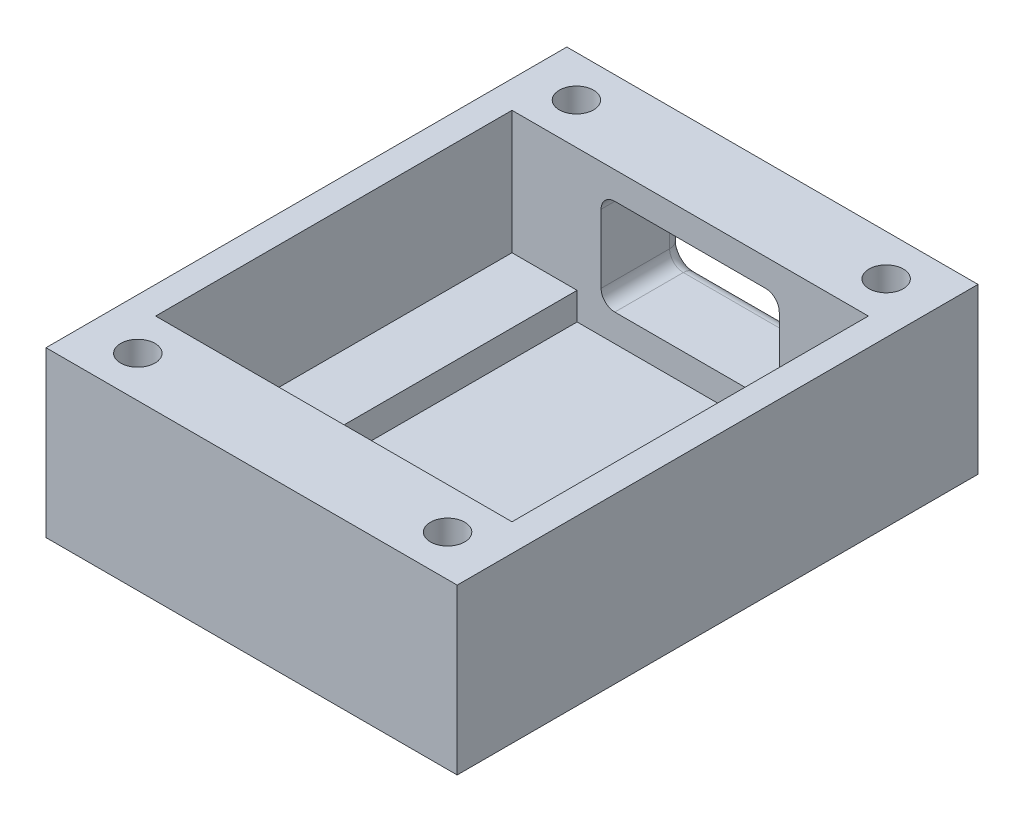
SolidWorks part; units mm, degrees
ref_plane "前视基准面" through (0, 0, 0) normal (0, 0, 1) x (1, 0, 0)
ref_plane "上视基准面" through (0, 0, 0) normal (0, 1, 0) x (1, 0, 0)
ref_plane "右视基准面" through (0, 0, 0) normal (1, 0, 0) x (0, 0, -1)
sketch "草图1" plane through (0, 0, 0) normal (0, 1, 0) x (1, 0, 0)
  line L0 (-50.4212, 0) -> (58.0073, 0) construction
  line L1 (-15, 19) -> (15, 19)
  line L2 (-15, 19) -> (-15, -19)
  line L3 (-15, -19) -> (15, -19)
  line L4 (15, 19) -> (15, -19)
  line L5 (0, 45.3104) -> (0, -50.4975) construction
  line L6 (-8.25, 13) -> (-8.25, -13)
  line L7 (-13, 13) -> (13, 13)
  line L8 (-13, 13) -> (-13, -13)
  line L9 (-13, -13) -> (13, -13)
  line L10 (13, 13) -> (13, -13)
  line L15 (8.25, 13) -> (8.25, -13)
  circle A0 centre (-11.3, 16) radius 1.25
  circle A1 centre (11.3, 16) radius 1.25
  circle A2 centre (11.3, -16) radius 1.25
  circle A3 centre (-11.3, -16) radius 1.25
  circle A4 centre (-11.3, 16) radius 2.25
  circle A5 centre (11.3, 16) radius 2.25
  circle A6 centre (11.3, -16) radius 2.25
  circle A7 centre (-11.3, -16) radius 2.25
  point P18 (-8.25, 13)
  point P19 (8.25, 13)
  point P20 (8.25, -13)
  point P21 (-8.25, -13)
  dimension "D5" = 2.5
  dimension "D6" = 4.5
  dimension "D1" = 26
  dimension "D2" = 16.5
  dimension "D3" = 30
  dimension "D4" = 38
  dimension "D7" = 3
  dimension "D8" = 3.7
extrude "凸台-拉伸1" add sketch "草图1" along normal blind 12 contours L1 L4 L3 L2
ref_plane "基准面1" through (0, 3, 0) normal (0, 1, 0) x (1, 0, 0)
extrude "切除-拉伸1" cut sketch "草图1<4>" along normal blind 14 from surface contours L8 L9 L10 L7 starting at plane "基准面1"
sketch "草图1<4>" plane through (0, 0, 0) normal (0, 1, 0) x (1, 0, 0) same geometry as "草图1"
extrude "切除-拉伸2" cut sketch "草图1<6>" against normal blind 2 from surface contours L15 L7 L6 L9 region at (0, 0, 0) starting at plane "基准面1"
sketch "草图1<6>" plane through (0, 0, 0) normal (0, 1, 0) x (1, 0, 0) same geometry as "草图1"
extrude "切除-拉伸5" cut sketch "草图1<7>" along normal blind 21 contours A0 | A1 | A3 | A2
sketch "草图1<7>" plane through (0, 0, 0) normal (0, 1, 0) x (1, 0, 0) same geometry as "草图1"
extrude "切除-拉伸6" cut sketch "草图1<8>" along normal blind 5 contours A4 | A7 | A5 | A6
sketch "草图1<8>" plane through (0, 0, 0) normal (0, 1, 0) x (1, 0, 0) same geometry as "草图1"
ref_plane "基准面3" through (0, 0, -19) normal (0, 0, 1) x (1, 0, 0)
sketch "草图3" plane through (0, 0, -19) normal (0, 0, 1) x (1, 0, 0)
  line L0 (0, 0) -> (0, 12.0168) construction
  line L1 (6.5, 10) -> (-6.5, 10)
  line L2 (6.5, 10) -> (6.5, 3)
  line L3 (6.5, 3) -> (-6.5, 3)
  line L4 (-6.5, 10) -> (-6.5, 3)
  line L5 (-15, 0) -> (15, 0) construction
  line L6 (8.25, 1) -> (-8.25, 1) construction
  dimension "D1" = 7
  dimension "D2" = 2
  dimension "D3" = 13
extrude "切除-拉伸7" cut sketch "草图3" along normal blind 7
fillet "圆角1" radius 1 4 edges at (6.5, 3, -16) (6.5, 10, -16) (-6.5, 10, -16) (-6.5, 3, -16)
fillet "圆角2" radius 1 8 edges at (6.2071, 9.7071, -19) (6.5, 6.5, -19) (6.2071, 3.2929, -19) (0, 3, -19) (-6.2071, 3.2929, -19) (-6.5, 6.5, -19) (-6.2071, 9.7071, -19) (0, 10, -19)
